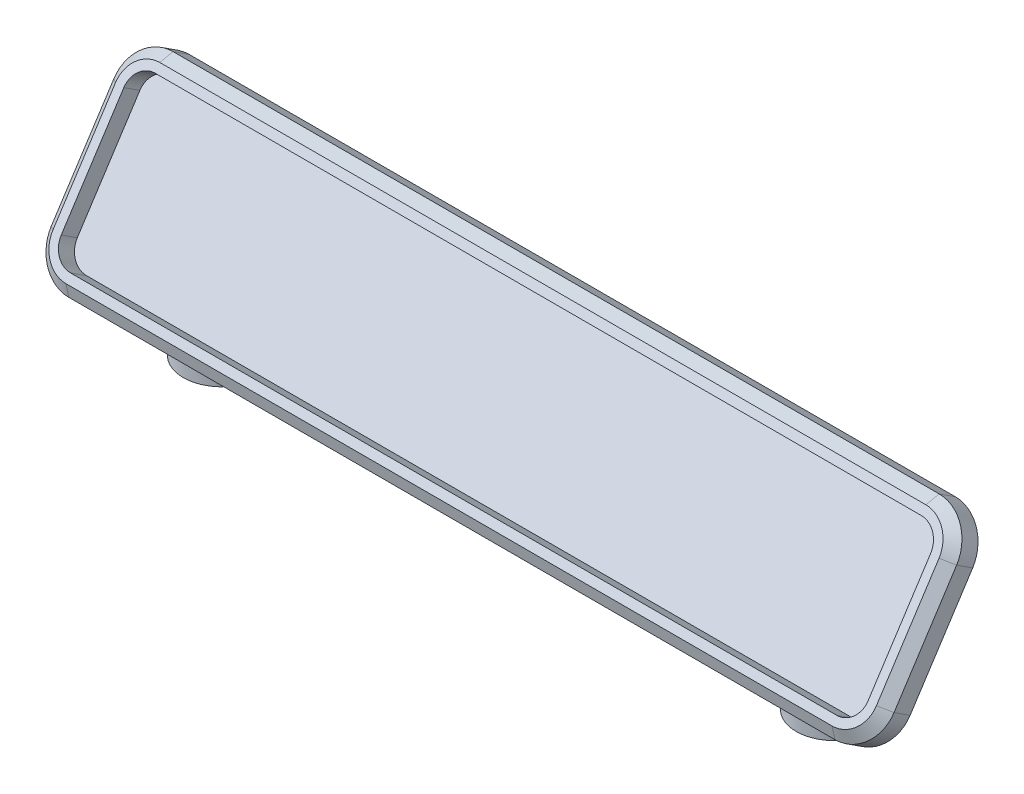
SolidWorks part; units mm, degrees
ref_plane "Front Plane" through (0, 0, 0) normal (0, 0, 1) x (1, 0, 0)
ref_plane "Top Plane" through (0, 0, 0) normal (0, 1, 0) x (1, 0, 0)
ref_plane "Right Plane" through (0, 0, 0) normal (1, 0, 0) x (0, 0, -1)
sketch "Sketch2" plane through (0, 0, 0) normal (0, 1, 0) x (1, 0, 0)
  line L0 (50.8, 0) -> (-50.8, 0) construction
  circle A0 centre (-50.8, 0) radius 6.35
  circle A1 centre (50.8, 0) radius 6.35
  point P8 (0, 0)
  dimension "D2" = 12.7
  dimension "D1" = 101.6
extrude "Boss-Extrude1" add sketch "Sketch2" along normal blind 19.05
ref_plane "Plane1" through (0, 19.05, 0) normal (0, 1, 0) x (1, 0, 0)
ref_axis "Axis1" through (88.99, 19.05, 0) along (-1, 0, 0)
ref_plane "Plane2" through (0, 5.6508, 8.7015) normal (0, 0.5446, 0.8387) x (-1, 0, 0)
sketch "Sketch3" plane through (0, 5.6508, 8.7015) normal (0, 0.5446, 0.8387) x (-1, 0, 0)
  line L0 (-50.8, -15.9767) -> (50.8, -15.9767)
  line L2 (-63.5, -31.8517) -> (63.5, -31.8517)
  line L3 (-69.85, -25.5017) -> (-69.85, -6.4517)
  line L4 (-63.5, -0.1017) -> (63.5, -0.1017)
  line L5 (69.85, -25.5017) -> (69.85, -6.4517)
  line L6 (-69.85, -31.8517) -> (69.85, -0.1017) construction
  line L7 (-69.85, -0.1017) -> (69.85, -31.8517) construction
  arc A0 (63.5, -0.1017) -> (69.85, -6.4517) centre (63.5, -6.4517) cw
  arc A1 (63.5, -31.8517) -> (69.85, -25.5017) centre (63.5, -25.5017) ccw
  arc A2 (-63.5, -31.8517) -> (-69.85, -25.5017) centre (-63.5, -25.5017) cw
  arc A3 (-69.85, -6.4517) -> (-63.5, -0.1017) centre (-63.5, -6.4517) cw
  ellipse E0 centre (50.8, -15.9767) end of major axis (44.45, -15.9767) minor radius 3.4585 construction
  ellipse E1 centre (-50.8, -15.9767) end of major axis (-57.15, -15.9767) minor radius 3.4585 construction
  ellipse E2 centre (50.8, -15.9767) end of major axis (44.45, -15.9767) minor radius 3.4585 construction
  ellipse E3 centre (-50.8, -15.9767) end of major axis (-57.15, -15.9767) minor radius 3.4585 construction
  point P22 (0, -15.9767)
  dimension "D3" = 6.35
  dimension "D1" = 139.7
  dimension "D2" = 31.75
extrude "Boss-Extrude2" add sketch "Sketch3" along normal blind 6.35 contours L2 L5 L4 L3 region at (66.9771, 29.9545, -7.0815)
sketch "Sketch8" plane through (0, 19.05, 0) normal (0, 1, 0) x (1, 0, 0)
  line L0 (44.45, 0) -> (57.15, 0) construction
  line L1 (-57.15, 0) -> (-44.45, 0) construction
  line L2 (44.45, 0) -> (57.15, 0)
  line L3 (-57.15, 0) -> (-44.45, 0)
  arc A0 (57.15, 0) -> (44.45, 0) centre (50.8, 0) ccw construction
  arc A1 (-44.45, 0) -> (-57.15, 0) centre (-50.8, 0) ccw construction
  arc A2 (57.15, 0) -> (44.45, 0) centre (50.8, 0) ccw
  arc A3 (-44.45, 0) -> (-57.15, 0) centre (-50.8, 0) ccw
  arc M1 (-44.45, 0) -> (-57.15, 0) centre (-50.8, 0) ccw
  line M2 (-57.15, 0) -> (-44.45, 0)
extrude "Boss-Extrude3" add sketch "Sketch8" along normal up to next contours L2 A2 | M2 M1 region at (50.8, 19.05, -2.695) region at (-50.8, 19.05, -2.695)
sketch "Sketch9" plane through (0, 9.1093, 14.0271) normal (0, 0.5446, 0.8387) x (1, 0, 0)
  line L8 (63.5, 28.8767) -> (-63.5, 28.8767)
  line L9 (-66.875, 25.5017) -> (-66.875, 6.4517)
  line L10 (-63.5, 3.0767) -> (63.5, 3.0767)
  line L11 (66.875, 6.4517) -> (66.875, 25.5017)
  line L12 (63.5, 28.8767) -> (-63.5, 28.8767)
  line L13 (-66.875, 25.5017) -> (-66.875, 6.4517)
  line L14 (-63.5, 3.0767) -> (63.5, 3.0767)
  line L15 (66.875, 6.4517) -> (66.875, 25.5017)
  arc A4 (63.5, 3.0767) -> (66.875, 6.4517) centre (63.5, 6.4517) ccw
  arc A5 (63.5, 3.0767) -> (66.875, 6.4517) centre (63.5, 6.4517) ccw
  arc A6 (66.875, 25.5017) -> (63.5, 28.8767) centre (63.5, 25.5017) ccw
  arc A7 (66.875, 25.5017) -> (63.5, 28.8767) centre (63.5, 25.5017) ccw
  arc A8 (-63.5, 28.8767) -> (-66.875, 25.5017) centre (-63.5, 25.5017) ccw
  arc A9 (-63.5, 28.8767) -> (-66.875, 25.5017) centre (-63.5, 25.5017) ccw
  arc A10 (-66.875, 6.4517) -> (-63.5, 3.0767) centre (-63.5, 6.4517) ccw
  arc A11 (-66.875, 6.4517) -> (-63.5, 3.0767) centre (-63.5, 6.4517) ccw
  dimension "D1" = 2.975
extrude "Cut-Extrude1" cut sketch "Sketch9" against normal blind 3.175
chamfer "Chamfer2" distance 1.5875 angle 45 16 edges at (-69.85, 19.05, 0) (0, 32.3639, -8.6461) (69.85, 19.05, 0) (0, 5.7361, 8.6461) (0, 9.1946, 13.9717) (-69.85, 22.5085, 5.3256) (69.85, 22.5085, 5.3256) (0, 35.8224, -3.3206) (67.9901, 30.8041, -7.6332) (-67.9901, 30.8041, -7.6332) (67.9901, 7.2959, 7.6332) (-67.9901, 7.2959, 7.6332) (67.9901, 10.7544, 12.9587) (-67.9901, 10.7544, 12.9587) (67.9901, 34.2625, -2.3076) (-67.9901, 34.2625, -2.3076)
hole_wizard "Hole1" positions "3DSketch1" profile "Sketch10" legacy
sketch3d "3DSketch1"
  line L0 (-50.8, 28.8281, 0) -> (-50.8, 0, 0) construction
  line L1 (50.8, 28.8281, 0) -> (50.8, 0, 0) construction
  point P0 (-50.8, 0, 0)
  point P4 (50.8, 0, 0)
sketch "Sketch10" plane through (-50.8, 0, 0) normal (1, 0, 0) x (0, 0, -1)
  line L0 (0, 0) -> (0, 10.16)
  line L1 (0, 10.16) -> (2.54, 10.16)
  line L2 (2.54, 10.16) -> (2.54, 0.6858)
  line L3 (2.54, 0.6858) -> (3.175, 0.6858)
  line L4 (3.175, 0.6858) -> (3.175, 0)
  line L5 (3.175, 0) -> (0, 0)
  line L6 (0, 110) -> (0, -10) construction
  dimension "Diameter" = 5.08
  dimension "Depth" = 10.16
  dimension "C-Bore Diameter" = 6.35
  dimension "C-Bore Depth" = 0.6858
